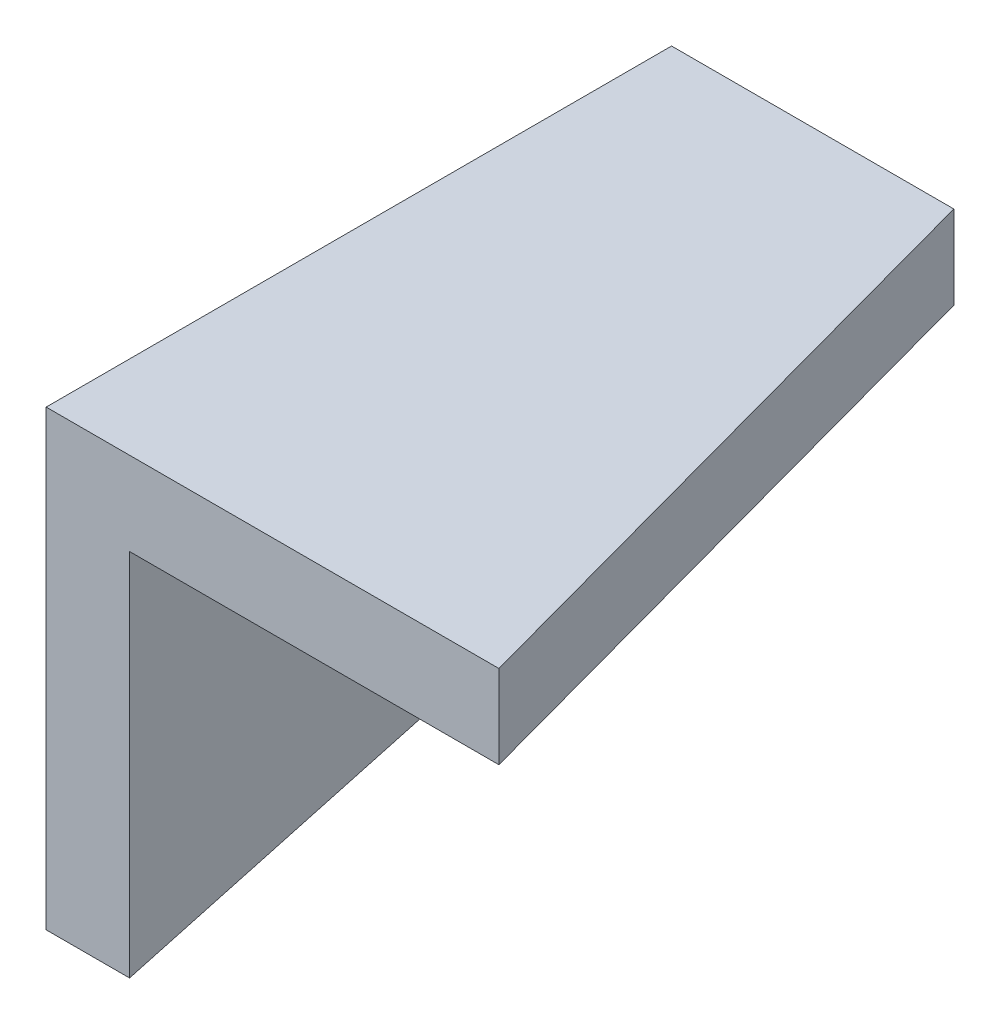
SolidWorks part; units mm, degrees
material "PLA"
ref_plane "Front Plane" through (0, 0, 0) normal (0, 0, 1) x (1, 0, 0)
ref_plane "Top Plane" through (0, 0, 0) normal (0, 1, 0) x (1, 0, 0)
ref_plane "Right Plane" through (0, 0, 0) normal (1, 0, 0) x (0, 0, -1)
sketch "Sketch1" plane through (0, 0, 0) normal (0, 0, 1) x (1, 0, 0)
  line L0 (40, 0) -> (0, 0)
  line L1 (0, 0) -> (0, -40)
  line L2 (40, 8) -> (-8, 8)
  line L3 (-8, 8) -> (-8, -40)
  line L4 (40, 0) -> (40, 8)
  line L5 (0, -40) -> (-8, -40)
  dimension "D1" = 40
  dimension "D2" = 40
  dimension "D3" = 8
extrude "Boss-Extrude1" add sketch "Sketch1" along normal mid plane 60
sketch "Sketch2" plane through (0, 0, 0) normal (0, -1, 0) x (1, 0, 0)
  line L0 (35.4354, 30) -> (19.0806, -30)
  line L1 (0, 30) -> (40, 30) construction
  line L2 (159.4514, 484.9707) -> (3.175, -88.3521) construction
  line L3 (0, -30) -> (40, -30) construction
  line L4 (19.0806, -30) -> (40, -30)
  line L5 (40, -30) -> (40, 30)
  line L6 (40, 30) -> (35.4354, 30)
extrude "Cut-Extrude1" cut sketch "Sketch2" against normal blind 10
sketch "Sketch4" plane through (0, 0, -30) normal (0, 0, -1) x (-1, 0, 0)
  line L0 (0, 0) -> (8, 8)
  line L1 (0, 0) -> (0, -40)
  line L2 (0, -40) -> (8, -40)
  line L3 (8, -40) -> (8, 8)
extrude "Cut-Extrude2" cut sketch "Sketch4" against normal through all
mirror "Mirror1" about plane through (0, 0, 30) normal (0.7071, 0.7071, 0) of bodies 104
